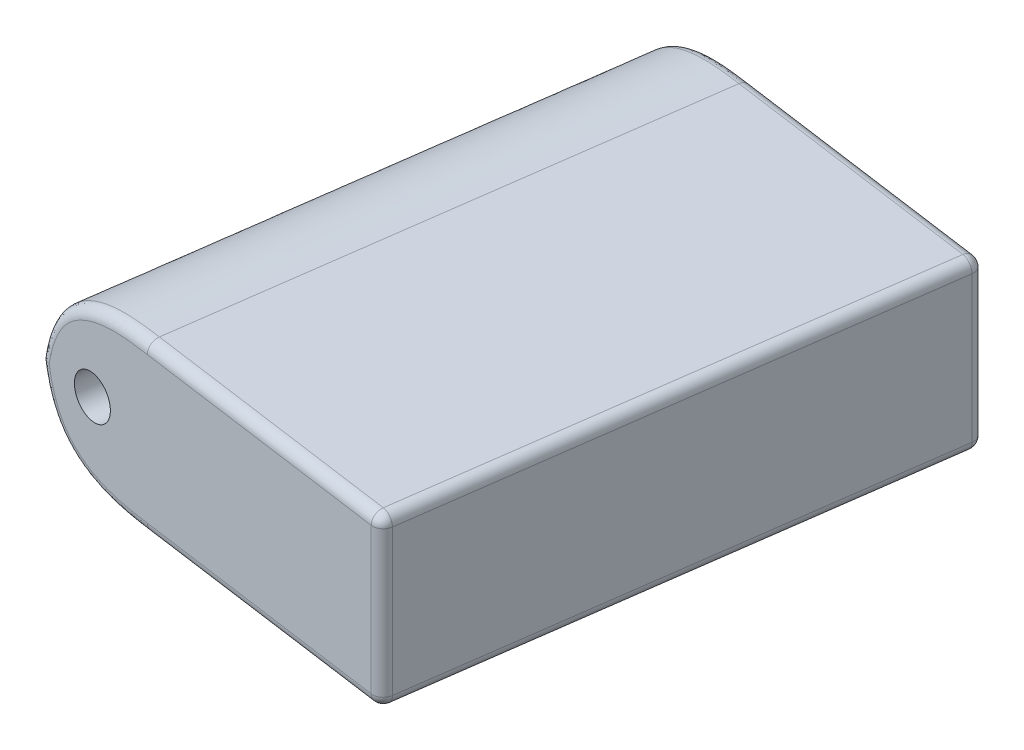
SolidWorks part; units mm, degrees
ref_plane "Front Plane" through (0, 0, 0) normal (0, 0, 1) x (1, 0, 0)
ref_plane "Top Plane" through (0, 0, 0) normal (0, 1, 0) x (1, 0, 0)
ref_plane "Right Plane" through (0, 0, 0) normal (1, 0, 0) x (0, 0, -1)
sketch "Sketch1" plane through (0, 0, 0) normal (0, 1, 0) x (1, 0, 0)
  line L12 (-29.6265, -8.5598) -> (-45.2825, -6.4414) construction
  line L13 (-26.8764, 11.317) -> (-29.6265, -8.5598) construction
  line L14 (-42.6007, 13.378) -> (-26.8764, 11.317) construction
  line L15 (-42.6007, 13.378) -> (-45.2825, -6.4414) construction
  line L20 (-27.4227, -19.1199) -> (-46.293, -16.509)
  line L21 (-23.9416, 6.0405) -> (-27.4227, -19.1199)
  line L22 (-42.8119, 8.6513) -> (-23.9416, 6.0405)
  line L23 (-42.8119, 8.6513) -> (-46.293, -16.509)
extrude "Boss-Extrude1" add sketch "Sketch1" along normal blind 7.9375
sketch "Sketch3" plane through (0.3167, 0, -2.6841) normal (0.1371, 0, -0.9906) x (-0.9906, 0, -0.1371)
  line L0 (40.4955, 3.9688) -> (43.5394, 3.9688) construction
  line L1 (43.5394, 7.9375) -> (43.5394, 0) construction
  line L3 (43.5394, 3.9688) -> (43.5394, 7.9375) construction
  circle A3 centre (40.4955, 3.9688) radius 2.032
extrude "Cut-Extrude1" cut sketch "Sketch3" against normal blind 2.7
sketch "Sketch4" plane through (0.0003, 0, -0.0022) normal (0.1371, 0, -0.9906) x (-0.9906, 0, -0.1371)
  circle A0 centre (40.5497, 3.9688) radius 1
extrude "Cut-Extrude2" cut sketch "Sketch4" against normal through all
fillet "Fillet2" radius 6.096 2 edges at (-44.5524, 0, 3.9289) (-44.5524, 7.9375, 3.9289)
fillet "Fillet3" radius 0.508 12 edges at (-25.6822, 0, 6.5397) (-25.6822, 7.9375, 6.5397) (-27.4227, 3.9688, 19.1199) (-23.9416, 3.9688, -6.0405)
